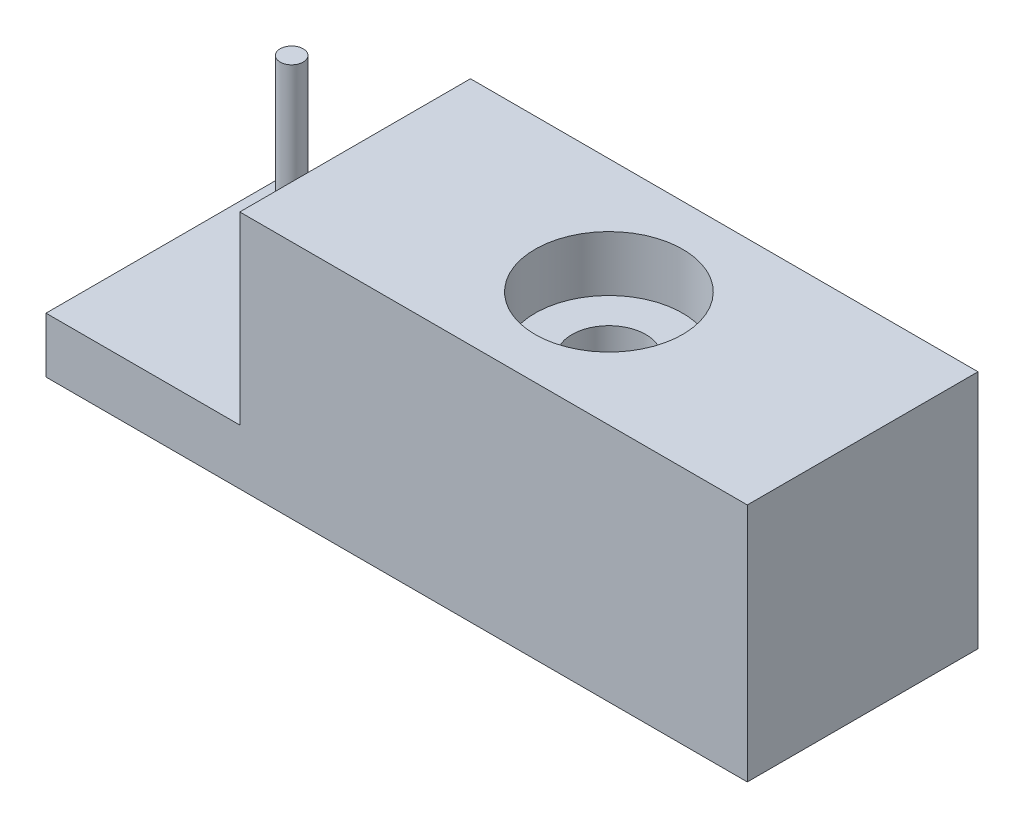
SolidWorks part; units mm, degrees
ref_plane "Front Plane" through (0, 0, 0) normal (0, 0, 1) x (1, 0, 0)
ref_plane "Top Plane" through (0, 0, 0) normal (0, 1, 0) x (1, 0, 0)
ref_plane "Right Plane" through (0, 0, 0) normal (1, 0, 0) x (0, 0, -1)
sketch "Sketch1" plane through (0, 0, 0) normal (0, 0, 1) x (1, 0, 0)
  line L0 (0, 0) -> (152, 0)
  line L1 (152, 0) -> (152, 52)
  line L2 (152, 52) -> (0, 52)
  line L3 (0, 52) -> (0, 0)
  dimension "D1" = 52
  dimension "D2" = 152
extrude "Boss-Extrude1" add sketch "Sketch1" against normal blind 50
sketch "Sketch2" plane through (0, 0, 0) normal (0, 0, 1) x (1, 0, 0)
  line L0 (0, 52) -> (0, 12)
  line L1 (0, 52) -> (0, 0) construction
  line L2 (0, 12) -> (42, 12)
  line L3 (42, 12) -> (42, 52)
  line L5 (42, 52) -> (0, 52)
  dimension "D1" = 40
  dimension "D2" = 42
  dimension "D3" = 40
extrude "Cut-Extrude1" cut sketch "Sketch2" against normal through all
sketch "Sketch3" plane through (0, 52, 0) normal (0, 1, 0) x (1, 0, 0)
  circle A0 centre (97, 25) radius 16
  dimension "D1" = 32
extrude "Cut-Extrude2" cut sketch "Sketch3" against normal blind 12
ref_plane "Plane1" through (0, 26, 0) normal (0, 1, 0) x (1, 0, 0)
mirror "Mirror1" about plane through (0, 26, 0) normal (0, 1, 0) of "Cut-Extrude2"
sketch "Sketch4" plane through (0, 40, 0) normal (0, 1, 0) x (1, 0, 0)
  circle A1 centre (97, 25) radius 8
  dimension "D1" = 16
extrude "Cut-Extrude3" cut sketch "Sketch4" against normal through all
ref_plane "Plane2" through (0, 52, 0) normal (0, 1, 0) x (1, 0, 0)
sketch "Sketch6" plane through (0, 52, 0) normal (0, 1, 0) x (1, 0, 0)
  line L0 (42, 25) -> (28.25, 25) construction
  line L1 (42, 50) -> (42, 0) construction
  circle A0 centre (28.25, 25) radius 2.5
  dimension "D2" = 5
  dimension "D1" = 13.75
extrude "Boss-Extrude2" add sketch "Sketch6" against normal up to surface (40 mm away) and the other way blind 10 up to face at (21, 12, -25)
